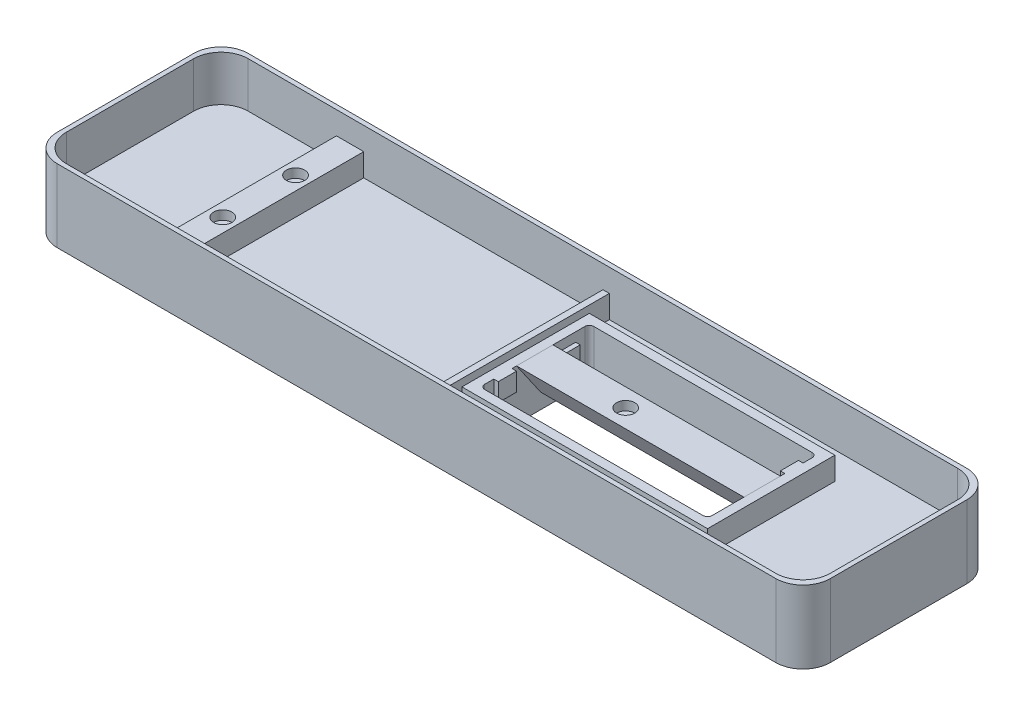
SolidWorks part; units mm, degrees
material "PVB"
ref_plane "Front Plane" through (0, 0, 0) normal (0, 0, 1) x (1, 0, 0)
ref_plane "Top Plane" through (0, 0, 0) normal (0, 1, 0) x (1, 0, 0)
ref_plane "Right Plane" through (0, 0, 0) normal (1, 0, 0) x (0, 0, -1)
ref_axis "X-axis" through (-88.99, 0, 0) along (1, 0, 0)
ref_axis "Y-axis" through (0, 55, 0) along (0, -1, 0)
ref_axis "Z-axis" through (0, 0, -88.99) along (0, 0, 1)
sketch "Sketch1" plane through (0, 0, 0) normal (0, 1, 0) x (1, 0, 0)
  line L1 (-107.95, 26.67) -> (107.95, 26.67)
  line L2 (-107.95, 26.67) -> (-107.95, -26.67)
  line L3 (-107.95, -26.67) -> (107.95, -26.67)
  line L4 (107.95, 26.67) -> (107.95, -26.67)
  line L5 (-107.95, 26.67) -> (107.95, -26.67) construction
  line L6 (-107.95, -26.67) -> (107.95, 26.67) construction
  point P0 (0, 0)
  dimension "D1" = 215.9
  dimension "D2" = 53.34
extrude "Boss-Extrude1" add sketch "Sketch1" along normal mid plane 20.32
sketch "Sketch3" plane through (0, 10.16, 0) normal (0, 1, 0) x (1, 0, 0)
  line L0 (-107.95, 26.67) -> (-107.95, -26.67) construction
  line L1 (-106.68, 25.4) -> (106.68, 25.4)
  line L2 (-106.68, 25.4) -> (-106.68, -25.4)
  line L3 (-106.68, -25.4) -> (106.68, -25.4)
  line L4 (106.68, 25.4) -> (106.68, -25.4)
  line L5 (-106.68, 25.4) -> (106.68, -25.4) construction
  line L6 (-106.68, -25.4) -> (106.68, 25.4) construction
  line L8 (107.95, 26.67) -> (-107.95, 26.67) construction
  point P0 (0, 0)
  dimension "D1" = 1.27
  dimension "D2" = 1.27
extrude "Cut-Extrude1" cut sketch "Sketch3" against normal blind 12.7
fillet "Fillet3" radius 7.62 8 edges at (106.68, 3.81, 25.4) (106.68, 3.81, -25.4) (-106.68, 3.81, 25.4) (-106.68, 3.81, -25.4) (-107.95, 0, 26.67) (107.95, 0, -26.67) (107.95, 0, 26.67) (-107.95, 0, -26.67)
sketch "Sketch4" plane through (0, -2.54, 0) normal (0, 1, 0) x (1, 0, 0)
  line L0 (99.06, 25.4) -> (-99.06, 25.4) construction
  line L1 (-74.422, 25.4) -> (-66.802, 25.4)
  line L2 (-74.422, 25.4) -> (-74.422, -25.4)
  line L3 (-74.422, -25.4) -> (-66.802, -25.4)
  line L4 (-66.802, 25.4) -> (-66.802, -25.4)
  line L5 (-99.06, -25.4) -> (99.06, -25.4) construction
  line L6 (-107.95, 19.05) -> (-107.95, -19.05) construction
  line L7 (0, 25.4) -> (1.778, 25.4)
  line L8 (0, 25.4) -> (0, -25.4)
  line L9 (0, -25.4) -> (1.778, -25.4)
  line L10 (1.778, 25.4) -> (1.778, -25.4)
  point P12 (-70.612, -25.4)
  dimension "D1" = 1.778
  dimension "D2" = 7.62
  dimension "D3" = 37.338
extrude "Boss-Extrude2" add sketch "Sketch4" along normal blind 6.35
sketch "Sketch5" plane through (0, -2.54, 0) normal (0, 1, 0) x (1, 0, 0)
  line L0 (107.95, -19.05) -> (107.95, 19.05) construction
  line L1 (3.81, 17.78) -> (72.39, 17.78)
  line L2 (3.81, 17.78) -> (3.81, -17.78)
  line L3 (3.81, -17.78) -> (72.39, -17.78)
  line L4 (72.39, 17.78) -> (72.39, -17.78)
  line L5 (3.81, 17.78) -> (72.39, -17.78) construction
  line L6 (3.81, -17.78) -> (72.39, 17.78) construction
  point P0 (38.1, 0)
  point P7 (0, 0)
  dimension "D1" = 35.56
  dimension "D2" = 35.56
  dimension "D3" = 68.58
extrude "Boss-Extrude3" add sketch "Sketch5" along normal blind 6.35
sketch "Sketch9" plane through (0, -2.54, 0) normal (0, 1, 0) x (1, 0, 0)
  line L0 (3.81, 17.78) -> (3.81, -17.78) construction
  line L1 (6.35, 15.24) -> (69.85, 15.24)
  line L2 (6.35, 15.24) -> (6.35, -15.24)
  line L3 (6.35, -15.24) -> (69.85, -15.24)
  line L4 (69.85, 15.24) -> (69.85, -15.24)
  line L5 (6.35, 15.24) -> (69.85, -15.24) construction
  line L6 (6.35, -15.24) -> (69.85, 15.24) construction
  line L7 (72.39, -17.78) -> (72.39, 17.78) construction
  line L8 (3.81, -17.78) -> (72.39, -17.78) construction
  line L9 (72.39, 17.78) -> (3.81, 17.78) construction
  point P0 (38.1, 0)
  dimension "D1" = 2.54
  dimension "D2" = 2.54
  dimension "D3" = 2.54
  dimension "D4" = 2.54
extrude "Cut-Extrude2" cut sketch "Sketch9" against normal through all both and the other way through all
sketch "Sketch10" plane through (0, 3.81, 0) normal (0, 1, 0) x (1, 0, 0)
  line L0 (6.35, -5.08) -> (69.85, -5.08)
  line L1 (6.35, 15.24) -> (6.35, -15.24) construction
  line L2 (69.85, -15.24) -> (69.85, 15.24) construction
  line L3 (69.85, -5.08) -> (69.85, 5.08)
  line L4 (69.85, 5.08) -> (6.35, 5.08)
  line L5 (6.35, 5.08) -> (6.35, -5.08)
  point P6 (6.35, 0)
  dimension "D1" = 5.08
extrude "Boss-Extrude4" add sketch "Sketch10" against normal blind 6.35 draft 28 from offset 0
sketch "Sketch11" plane through (6.35, 0, 0) normal (1, 0, 0) x (0, 0, -1)
  line L0 (-26.67, -10.16) -> (-26.67, 10.16) construction
  line L1 (-11.43, 3.81) -> (-6.35, 3.81)
  line L2 (-11.43, 3.81) -> (-11.43, -1.27)
  line L3 (-11.43, -1.27) -> (-6.35, -1.27)
  line L4 (-6.35, 3.81) -> (-6.35, -1.27)
  line L5 (6.35, 1.27) -> (11.43, 1.27)
  line L6 (6.35, 1.27) -> (6.35, -3.81)
  line L7 (6.35, -3.81) -> (11.43, -3.81)
  line L8 (11.43, 1.27) -> (11.43, -3.81)
  line L11 (-19.05, 10.16) -> (19.05, 10.16) construction
  dimension "D1" = 5.08
  dimension "D2" = 5.08
  dimension "D3" = 12.7
  dimension "D4" = 15.24
  dimension "D5" = 5.08
  dimension "D6" = 5.08
  dimension "D7" = 6.35
extrude "Boss-Extrude5" add sketch "Sketch11" along normal blind 1.27
sketch "Sketch13" plane through (69.85, 0, 0) normal (-1, 0, 0) x (0, 0, 1)
  line L1 (-11.43, 3.81) -> (-6.35, 3.81)
  line L2 (-11.43, 3.81) -> (-11.43, -1.27)
  line L3 (-11.43, -1.27) -> (-6.35, -1.27)
  line L4 (-6.35, 3.81) -> (-6.35, -1.27)
  line L5 (6.35, 1.27) -> (11.43, 1.27)
  line L6 (6.35, 1.27) -> (6.35, -3.81)
  line L7 (6.35, -3.81) -> (11.43, -3.81)
  line L8 (11.43, 1.27) -> (11.43, -3.81)
  line L9 (-19.05, 10.16) -> (19.05, 10.16) construction
  line L10 (-26.67, -10.16) -> (-26.67, 10.16) construction
  dimension "D1" = 5.08
  dimension "D2" = 5.08
  dimension "D3" = 12.7
  dimension "D4" = 15.24
  dimension "D5" = 5.08
  dimension "D6" = 5.08
  dimension "D7" = 6.35
extrude "Boss-Extrude6" add sketch "Sketch13" along normal blind 1.27
sketch "Sketch16" plane through (69.85, 0, 0) normal (-1, 0, 0) x (0, 0, 1)
  line L1 (-5.08, -7.62) -> (-5.08, -2.54)
  line L2 (-5.08, -2.54) -> (5.08, -2.54)
  line L3 (5.08, -2.54) -> (5.08, -7.62)
  line L4 (5.08, -7.62) -> (-5.08, -7.62)
extrude "Cut-Extrude3" cut sketch "Sketch16" against normal blind 1.27
fillet "Fillet4" radius 1.27 4 edges at (69.85, -3.175, -15.24) (69.85, -3.175, 15.24) (6.35, -3.175, 15.24) (6.35, -3.175, -15.24)
sketch "Sketch19" plane through (0, -10.16, 0) normal (0, -1, 0) x (1, 0, 0)
  line L0 (71.12, -5.08) -> (71.12, 5.08) construction
  circle A0 centre (71.12, 0) radius 5.08
extrude "Cut-Extrude5" cut sketch "Sketch19" against normal blind 0.508
sketch "Sketch21" plane through (6.35, 0, 0) normal (1, 0, 0) x (0, 0, -1)
  line L0 (-15.24, -10.16) -> (-15.24, 3.81) construction
  line L1 (-8.89, -10.033) -> (-12.7, -10.033)
  line L2 (-8.89, -10.033) -> (-8.89, -9.652)
  line L3 (-8.89, -9.652) -> (-12.7, -9.652)
  line L4 (-12.7, -10.033) -> (-12.7, -9.652)
  line L5 (8.89, -10.033) -> (12.7, -10.033)
  line L6 (8.89, -10.033) -> (8.89, -9.652)
  line L7 (8.89, -9.652) -> (12.7, -9.652)
  line L8 (12.7, -10.033) -> (12.7, -9.652)
  line L9 (15.24, 3.81) -> (15.24, -10.16) construction
  line L10 (13.97, -10.16) -> (-13.97, -10.16) construction
  point P14 (0, 0)
  dimension "D1" = 3.81
  dimension "D2" = 0.381
  dimension "D3" = 2.54
  dimension "D4" = 2.54
  dimension "D5" = 0.127
extrude "Cut-Extrude7" cut sketch "Sketch21" against normal blind 3.937
sketch "Sketch24" plane through (0, 3.81, 0) normal (0, 1, 0) x (1, 0, 0)
  line L0 (-100.33, -26.67) -> (100.33, -26.67) construction
  line L1 (100.33, 26.67) -> (-100.33, 26.67) construction
  circle A0 centre (-70.612, -10.16) radius 2.54
  circle A1 centre (-70.612, 10.16) radius 2.54
  dimension "D1" = 5.08
  dimension "D2" = 5.08
  dimension "D3" = 16.51
  dimension "D4" = 16.51
extrude "Cut-Extrude11" cut sketch "Sketch24" against normal blind 2.54
sketch "Sketch25" plane through (0, 3.81, 0) normal (0, 1, 0) x (1, 0, 0)
  line L0 (107.95, -19.05) -> (107.95, 19.05) construction
  line L1 (-70.612, 10.16) -> (-70.612, -10.16) construction
  circle A0 centre (31.75, 0) radius 2.54
  dimension "D1" = 76.2
  dimension "D2" = 5.08
extrude "Cut-Extrude12" cut sketch "Sketch25" against normal blind 2.54
